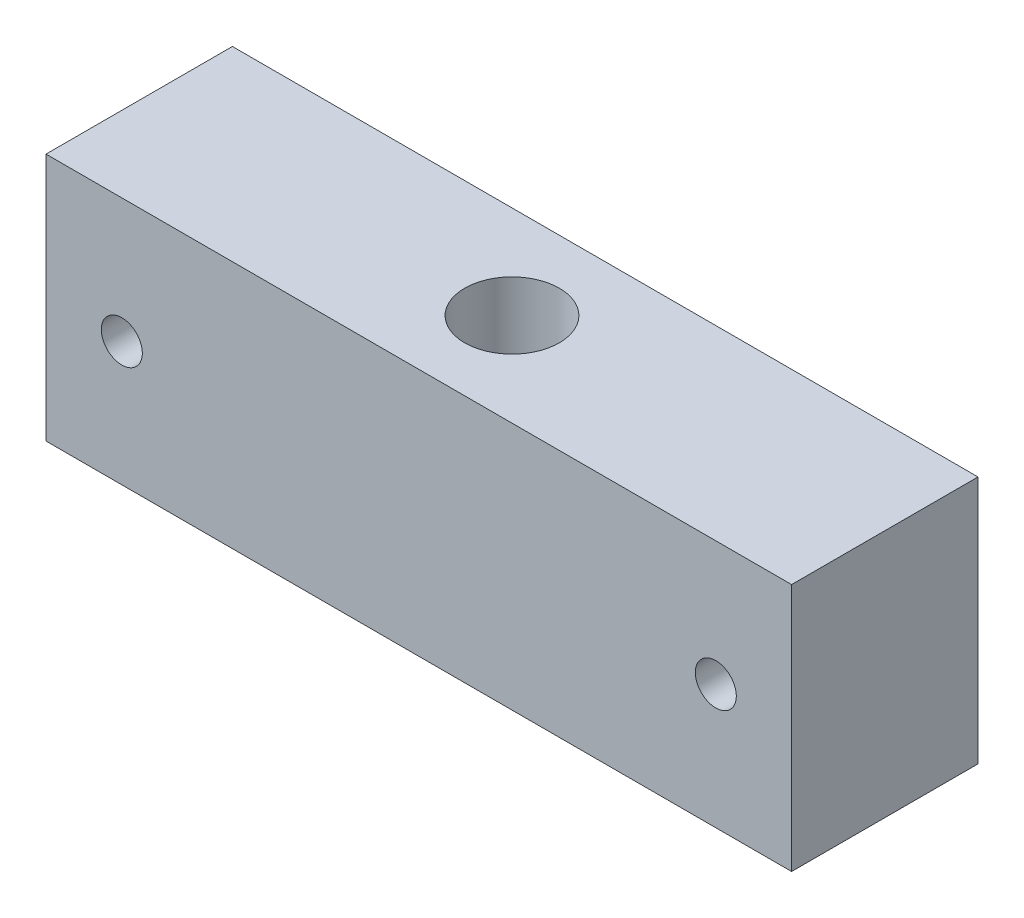
SolidWorks part; units mm, degrees
ref_plane "Front Plane" through (0, 0, 0) normal (0, 0, 1) x (1, 0, 0)
ref_plane "Top Plane" through (0, 0, 0) normal (0, 1, 0) x (1, 0, 0)
ref_plane "Right Plane" through (0, 0, 0) normal (1, 0, 0) x (0, 0, -1)
sketch "Sketch1" plane through (0, 0, 0) normal (0, 0, 1) x (1, 0, 0)
  line L1 (-30, 10) -> (30, 10)
  line L2 (-30, 10) -> (-30, -10)
  line L3 (-30, -10) -> (30, -10)
  line L4 (30, 10) -> (30, -10)
  line L5 (-30, 10) -> (30, -10) construction
  line L6 (-30, -10) -> (30, 10) construction
  point P0 (0, 0)
  dimension "D1" = 60
  dimension "D2" = 20
extrude "Boss-Extrude1" add sketch "Sketch1" along normal mid plane 15
sketch "Sketch3" plane through (0, 10, 0) normal (0, 1, 0) x (1, 0, 0)
  circle A0 centre (0, 0) radius 3.81
  dimension "D1" = 7.62
extrude "Cut-Extrude1" cut sketch "Sketch3" against normal through all
hole_wizard "M4x0.7 Tapped Hole1" positions "Sketch5" profile "Sketch6" tap size "M4x0.7" standard "ANSI Metric" end condition through all
sketch "Sketch5" plane through (0, 0, -7.5) normal (0, 0, -1) x (-1, 0, 0)
  line L0 (-23.9, 0) -> (23.9, 0) construction
  point P0 (-23.9, 0)
  point P2 (23.9, 0)
  point P8 (-2.767, 2.8614)
  dimension "D1" = 47.8
sketch "Sketch6" plane through (23.9, 0, -7.5) normal (1, 0, 0) x (0, 1, 0)
  line L0 (0, 0) -> (0, 15)
  line L1 (0, 15) -> (1.65, 15)
  line L2 (1.65, 15) -> (1.65, 0)
  line L5 (1.65, 0) -> (0, 0)
  line L11 (0, -6.35) -> (0, 107.95) construction
  dimension "Thru Tap Drill Dia." = 3.3
  dimension "Thru Tap Drill Depth" = 15
cosmetic thread "Hole Thread1" parameters "D2"=4
cosmetic thread "Hole Thread2" parameters "D2"=4
thread "Thread1" pitch 0.7 method cut profile "Thread Profile1" start angle 0, offset 0, length 10, pitch 0.7, diameter 3.3
ref_plane "Plane1" through (25.55, 0, -7.5) normal (0, -1, 0) x (1, 0, 0)
sketch "Thread Profile1" plane through (25.55, 0, -7.5) normal (0, -1, 0) x (1, 0, 0)
  line L0 (0, 0) -> (0, 0.7) construction
  line L1 (0, 0) -> (0.3789, 0.2187)
  line L2 (0.3789, 0.2187) -> (0.3789, 0.3062)
  line L3 (0.3789, 0.3062) -> (0, 0.525)
  line L4 (0.3789, 0.2625) -> (0, 0.2625) construction
  line L11 (0, 0) -> (0, 0.525)
  point P2 (0, 0)
  dimension "Pitch" = 0.7
  dimension "Profile_Angle" = 60
  dimension "Profile_Land" = 0.0875
  dimension "Profile_Height" = 0.3789
thread "Thread2" pitch 0.7 method cut profile "Thread Profile2" start angle 0, offset 0, length 10, pitch 0.7, diameter 3.3
ref_plane "Plane2" through (-22.25, 0, -7.5) normal (0, -1, 0) x (1, 0, 0)
sketch "Thread Profile2" plane through (-22.25, 0, -7.5) normal (0, -1, 0) x (1, 0, 0)
  line L0 (0, 0) -> (0, 0.7) construction
  line L1 (0, 0) -> (0.3789, 0.2187)
  line L2 (0.3789, 0.2187) -> (0.3789, 0.3062)
  line L3 (0.3789, 0.3062) -> (0, 0.525)
  line L4 (0.3789, 0.2625) -> (0, 0.2625) construction
  line L11 (0, 0) -> (0, 0.525)
  point P2 (0, 0)
  dimension "Pitch" = 0.7
  dimension "Profile_Angle" = 60
  dimension "Profile_Land" = 0.0875
  dimension "Profile_Height" = 0.3789
